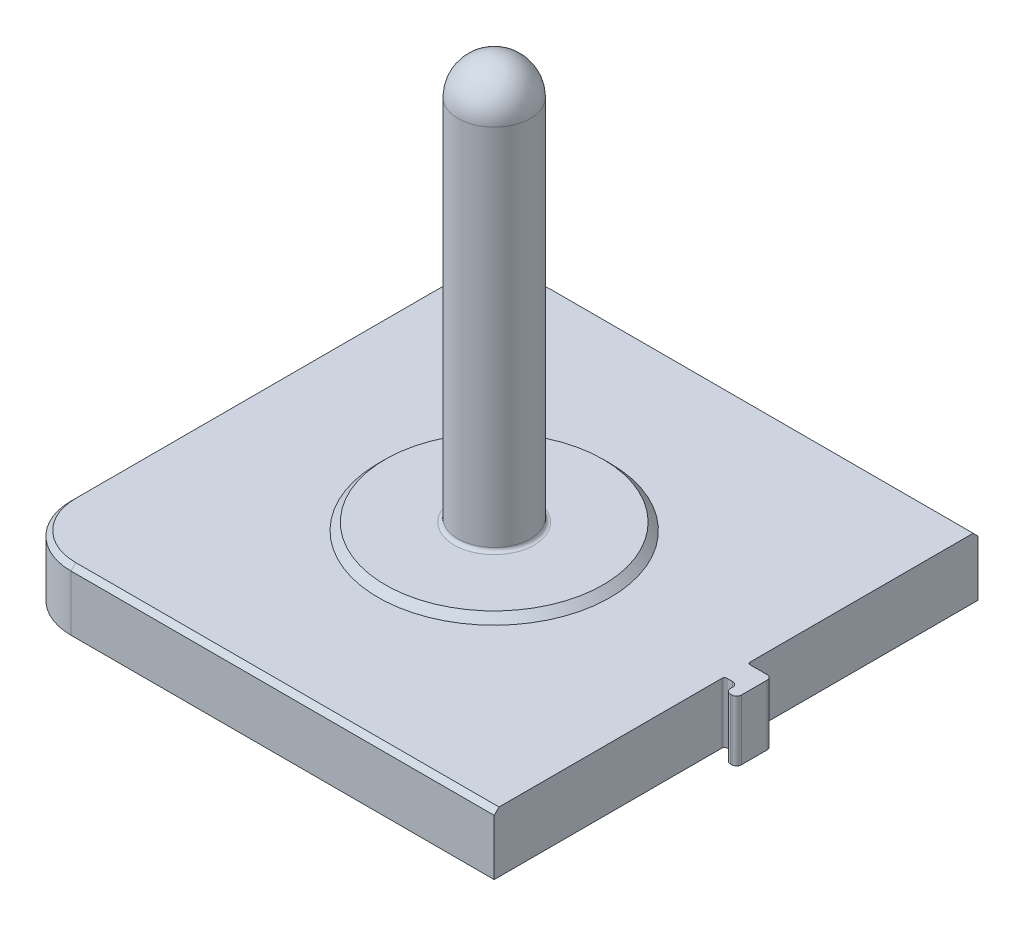
SolidWorks part; units mm, degrees
material "Custom Plastic"
ref_plane "Front Plane" through (0, 0, 0) normal (0, 0, 1) x (1, 0, 0)
ref_plane "Top Plane" through (0, 0, 0) normal (0, 1, 0) x (1, 0, 0)
ref_plane "Right Plane" through (0, 0, 0) normal (1, 0, 0) x (0, 0, -1)
sketch "Sketch1" plane through (0, 0, 0) normal (0, 1, 0) x (1, 0, 0)
  line L1 (100, -100) -> (-100, -100)
  line L2 (100, -100) -> (100, 100)
  line L3 (100, 100) -> (-100, 100)
  line L4 (-100, -100) -> (-100, 100)
  line L5 (100, -100) -> (-100, 100) construction
  line L6 (100, 100) -> (-100, -100) construction
  point P0 (0, 0)
  dimension "D1" = 200
  dimension "D2" = 200
extrude "Boss-Extrude1" add sketch "Sketch1" along normal blind 25
sketch "Sketch2" plane through (0, 25, 0) normal (0, 1, 0) x (1, 0, 0)
  circle A0 centre (0, 0) radius 15
  dimension "D1" = 30
extrude "Boss-Extrude2" add sketch "Sketch2" along normal blind 170
sketch "Sketch4" plane through (0, 0, 0) normal (0, 1, 0) x (1, 0, 0)
  line L0 (-1000, 0) -> (49000, 0) construction
  line L1 (100, -100) -> (100, 100) construction
  line L2 (100, -100) -> (100, 100) construction
  line L3 (100, 4.8) -> (108, 4.8)
  line L4 (110, 2.8) -> (110, -7.8)
  line L5 (108, -9.8) -> (107.4, -9.8)
  line L6 (105.4, -7.8) -> (105.4, -6.8)
  line L7 (103.4, -4.8) -> (100, -4.8)
  line L8 (100, -4.8) -> (100, 4.8)
  arc A0 (108, 4.8) -> (110, 2.8) centre (108, 2.8) cw
  arc A1 (110, -7.8) -> (108, -9.8) centre (108, -7.8) cw
  arc A2 (107.4, -9.8) -> (105.4, -7.8) centre (107.4, -7.8) cw
  arc A3 (105.4, -6.8) -> (103.4, -4.8) centre (103.4, -6.8) ccw
  point P7 (100, 0)
  point P15 (110, 4.8)
  point P18 (110, -9.8)
  point P21 (105.4, -9.8)
  point P24 (105.4, -4.8)
  dimension "D5" = 2
  dimension "D1" = 9.6
  dimension "D2" = 5.4
  dimension "D3" = 4.6
  dimension "D4" = 14.6
extrude "Boss-Extrude3" add sketch "Sketch4" along normal blind 25
fillet "Fillet1" radius 1 2 edges at (100, 12.5, -4.8) (100, 12.5, 4.8)
fillet "Fillet2" radius 25 2 edges at (-100, 12.5, -100) (-100, 12.5, 100)
fillet "Fillet3" radius 15 1 edges at (0, 195, 15)
sketch "Sketch5" plane through (0, 25, 0) normal (0, 1, 0) x (1, 0, 0)
  circle A0 centre (0, 0) radius 45
  dimension "D1" = 90
extrude "Boss-Extrude4" add sketch "Sketch5" along normal blind 3
chamfer "Chamfer1" distance 3 angle 45 1 edges at (0, 25, 45)
fillet "Fillet4" radius 1.5 1 edges at (0, 28, 15)
chamfer "Chamfer2" distance 2 angle 45 5 edges at (12.5, 25, -100) (-92.6777, 25, -92.6777) (-100, 25, 0) (-92.6777, 25, 92.6777) (12.5, 25, 100)
